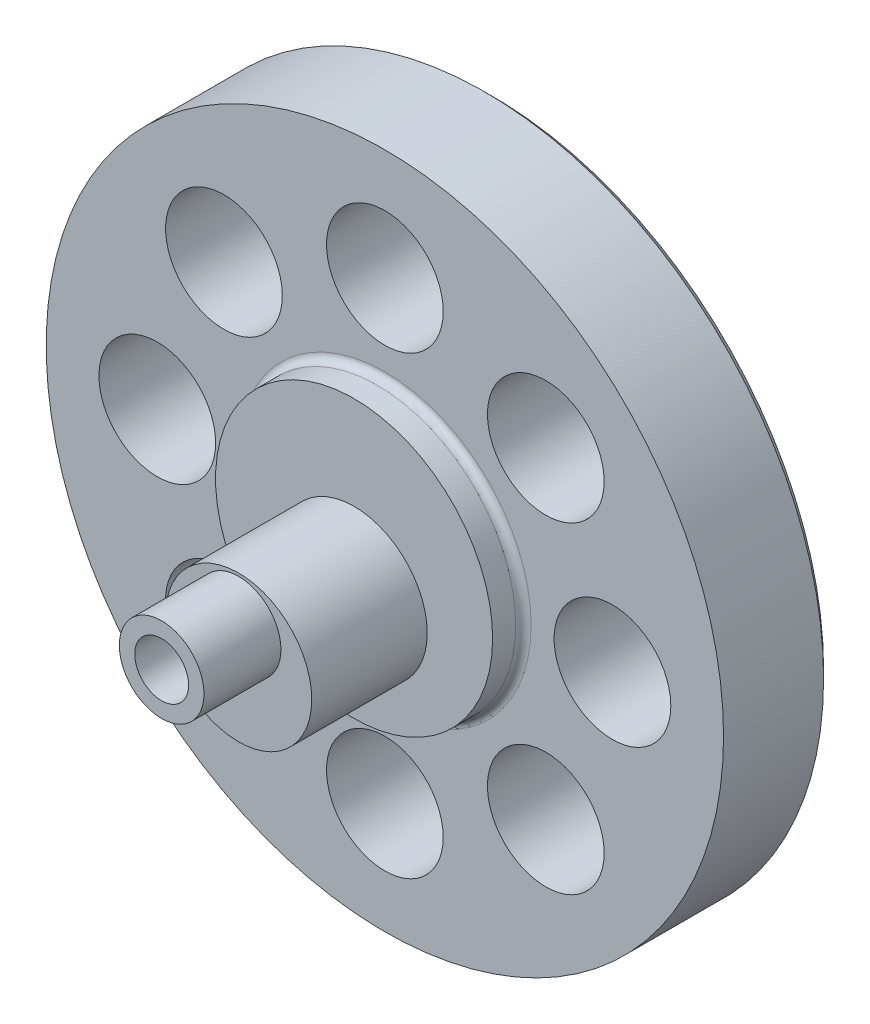
SolidWorks part; units mm, degrees
material "ABS PC"
ref_plane "Front Plane" through (0, 0, 0) normal (0, 0, 1) x (1, 0, 0)
ref_plane "Top Plane" through (0, 0, 0) normal (0, 1, 0) x (1, 0, 0)
ref_plane "Right Plane" through (0, 0, 0) normal (1, 0, 0) x (0, 0, -1)
sketch "Sketch1" plane through (0, 0, 0) normal (0, 0, 1) x (1, 0, 0)
  circle A2 centre (0, 0) radius 22
  circle A10 centre (-14.784, 0) radius 3.79
  circle A11 centre (-10.4538, -10.4538) radius 3.79
  circle A12 centre (0, -14.784) radius 3.79
  circle A13 centre (10.4538, -10.4538) radius 3.79
  circle A14 centre (14.784, 0) radius 3.79
  circle A15 centre (10.4538, 10.4538) radius 3.79
  circle A16 centre (0, 14.784) radius 3.79
  circle A17 centre (-10.4538, 10.4538) radius 3.79
  dimension "D1" = 7.58
  dimension "D2" = 44
extrude "Boss-Extrude1" add sketch "Sketch1" along normal blind 7
sketch "Sketch2" plane through (0, 0, 7) normal (0, 0, 1) x (1, 0, 0)
  circle A0 centre (0, 0) radius 9
  dimension "D1" = 18
extrude "Boss-Extrude2" add sketch "Sketch2" along normal blind 2
sketch "Sketch3" plane through (0, 0, 0) normal (0, 0, -1) x (-1, 0, 0)
  circle A0 centre (0, 0) radius 6.75
  dimension "D1" = 13.5
extrude "Cut-Extrude1" cut sketch "Sketch3" against normal blind 7
sketch "Sketch4" plane through (0, 0, 9) normal (0, 0, 1) x (1, 0, 0)
  circle A0 centre (0, -1.812) radius 4.75
  dimension "D2" = 9.5
  dimension "D1" = 1.812
extrude "Boss-Extrude3" add sketch "Sketch4" along normal blind 7.5
sketch "Sketch5" plane through (0, 0, 16.5) normal (0, 0, 1) x (1, 0, 0)
  circle A0 centre (0, 0) radius 2.75
  dimension "D1" = 5.5
extrude "Boss-Extrude4" add sketch "Sketch5" along normal blind 5
fillet "Fillet1" radius 0.5 1 edges at (9, 0, 7)
sketch "Sketch6" plane through (0, 0, 0) normal (0, 0, -1) x (-1, 0, 0)
  circle A0 centre (0, 0) radius 6.5
  circle A1 centre (0, 0) radius 3.5
  dimension "D1" = 7
extrude "Boss-Extrude5" [suppressed] add sketch "Sketch6" against normal blind 6
chamfer "Chamfer1" distance 0.5 angle 45 10 edges at (-6.6638, 10.4538, 0) (3.79, 14.784, 0) (14.2438, 10.4538, 0) (18.574, 0, 0) (14.2438, -10.4538, 0) (3.79, -14.784, 0) (-6.6638, -10.4538, 0) (-10.994, 0, 0) (22, 0, 0) (-6.75, 0, 0)
sketch "Sketch7" plane through (0, 0, 21.5) normal (0, 0, 1) x (1, 0, 0)
  circle A0 centre (0, 0) radius 1.75
  dimension "D1" = 3.5
extrude "Cut-Extrude2" cut sketch "Sketch7" against normal blind 15
